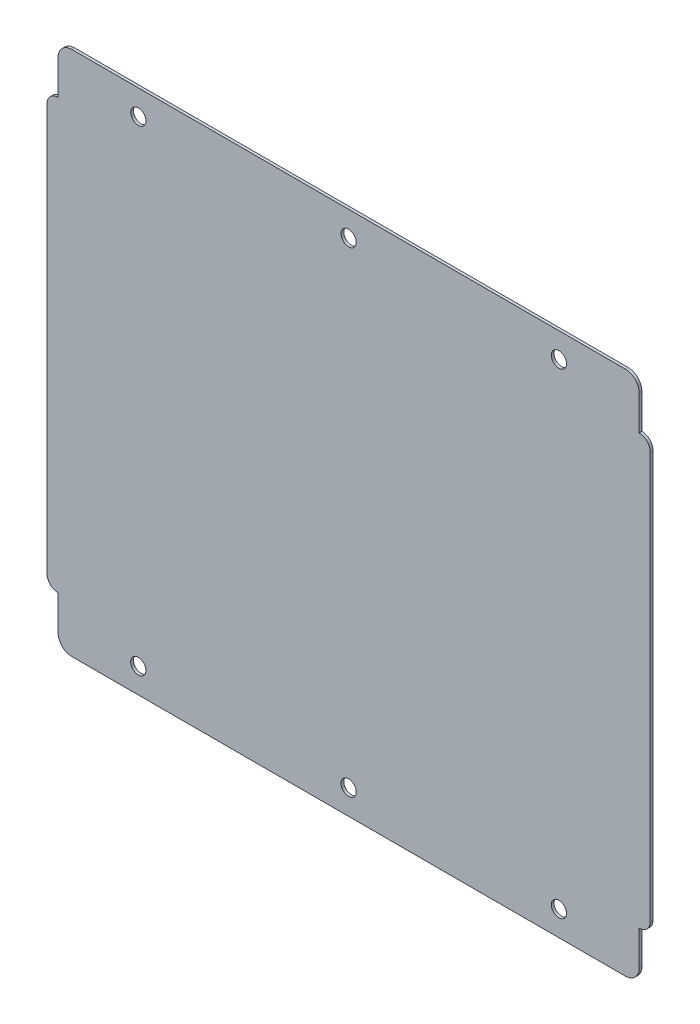
SolidWorks part; units mm, degrees
material "AISI 304"
ref_plane "Спереди" through (0, 0, 0) normal (0, 0, 1) x (1, 0, 0)
ref_plane "Сверху" through (0, 0, 0) normal (0, 1, 0) x (1, 0, 0)
ref_plane "Справа" through (0, 0, 0) normal (1, 0, 0) x (0, 0, -1)
sketch "Эскиз1" plane through (0, 0, 0) normal (0, 0, 1) x (1, 0, 0)
  line L0 (-210, 155) -> (-210, 190)
  line L1 (-218, -155) -> (-210, -155)
  line L2 (-218, -155) -> (-218, 155)
  line L3 (-218, 155) -> (-210, 155)
  line L4 (218, -155) -> (218, 155)
  line L5 (-218, -155) -> (218, 155) construction
  line L6 (-218, 155) -> (218, -155) construction
  line L7 (-210, 190) -> (210, 190)
  line L8 (0, -1.1) -> (0, 1.1) construction
  line L9 (210, 155) -> (210, 190)
  line L10 (1.1, 0) -> (-1.1, 0) construction
  line L11 (210, -155) -> (210, -190)
  line L12 (-210, -190) -> (210, -190)
  line L13 (-210, -155) -> (-210, -190)
  line L14 (210, 155) -> (218, 155)
  line L15 (210, -155) -> (218, -155)
  point P0 (0, 0)
  point P11 (0, 190)
  dimension "D3" = 380
  dimension "D1" = 310
  dimension "D2" = 436
  dimension "D4" = 8
extrude "Бобышка-Вытянуть1" add sketch "Эскиз1" along normal mid plane 2
fillet "Скругление1" radius 10 4 edges at (210, 190, 0) (210, -190, 0) (-210, -190, 0) (-210, 190, 0)
fillet "Скругление2" radius 8 4 edges at (-218, -155, 0) (-218, 155, 0) (218, 155, 0) (218, -155, 0)
sketch "Эскиз2" plane through (0, 0, 1) normal (0, 0, 1) x (1, 0, 0)
  line L0 (210, -172) -> (-210, -172) construction
  line L1 (210, -180) -> (210, -155) construction
  line L2 (-210, -155) -> (-210, -180) construction
  line L3 (-200, -190) -> (200, -190) construction
  line L4 (0, -1.1) -> (0, 1.1) construction
  line L5 (1.1, 0) -> (-1.1, 0) construction
  line L6 (210, 172) -> (-210, 172) construction
  circle A0 centre (0, -172) radius 5.5
  circle A1 centre (152, -172) radius 5.5
  circle A4 centre (-152, -172) radius 5.5
  circle A5 centre (-152, 172) radius 5.5
  circle A8 centre (152, 172) radius 5.5
  circle A9 centre (0, 172) radius 5.5
  dimension "D2" = 11
  dimension "D4" = 152
  dimension "D1" = 18
  dimension "D3" = 2
extrude "Вырез-Вытянуть1" cut sketch "Эскиз2" against normal blind 10
